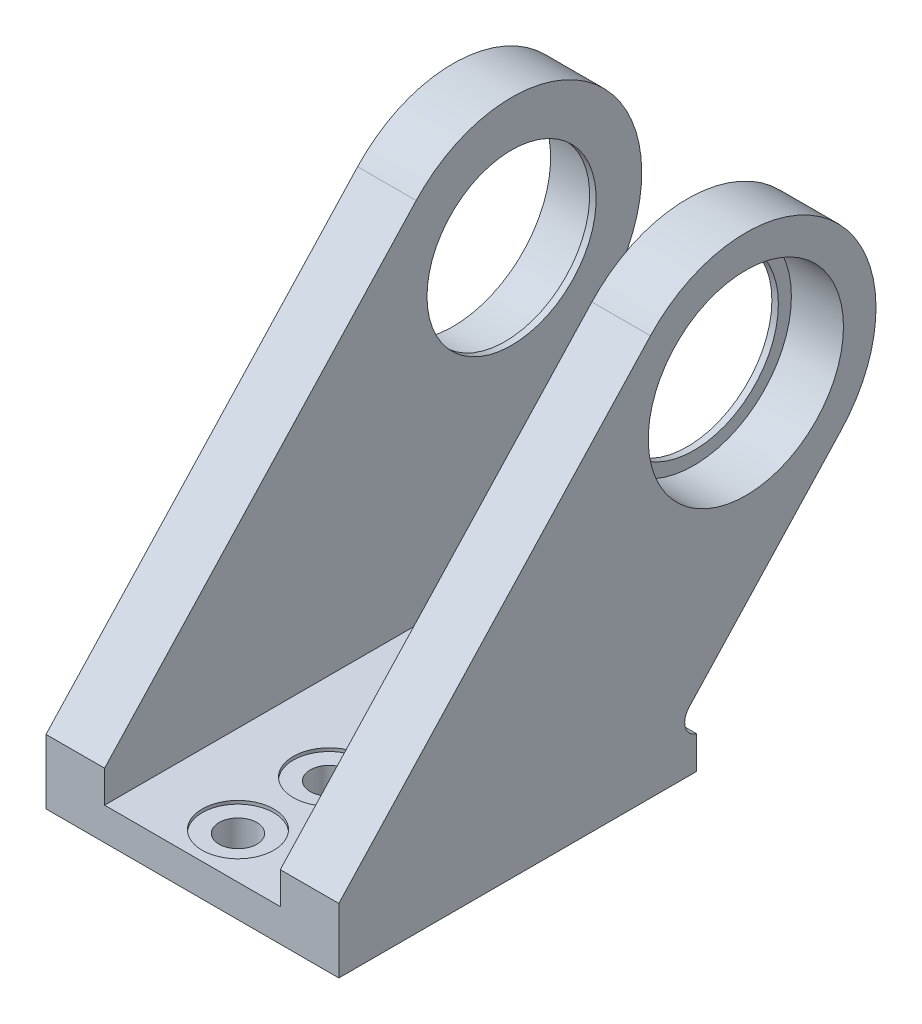
SolidWorks part; units mm, degrees
note: '?' marks a value the reader was unsure of.
ref_plane "前视基准面" through (0, 0, 0) normal (0, 0, 1) x (1, 0, 0)
ref_plane "上视基准面" through (0, 0, 0) normal (0, 1, 0) x (1, 0, 0)
ref_plane "右视基准面" through (0, 0, 0) normal (1, 0, 0) x (0, 0, -1)
sketch "草图1" plane through (0, 0, 0) normal (0, 1, 0) x (1, 0, 0)
  line L1 (0, 0) -> (45, 0)
  line L2 (0, 0) -> (0, 50)
  line L3 (0, 50) -> (45, 50)
  line L4 (45, 0) -> (45, 50)
  dimension "D1" = 50
  dimension "D2" = 45
extrude "凸台-拉伸1" add sketch "草图1" along normal blind 5
sketch "草图2" plane through (45, 0, 0) normal (1, 0, 0) x (0, 0, -1)
  line L0 (0, 5) -> (0, 9.9205)
  line L1 (0, 9.9205) -> (47.8837, 61.5289)
  line L2 (50, 5) -> (0, 5)
  line L3 (77.2063, 34.3226) -> (50, 5)
  arc A0 (77.2063, 34.3226) -> (47.8837, 61.5289) centre (62.545, 47.9258) ccw
  dimension "D1" = 40
  dimension "D2" = 40
extrude "凸台-拉伸2" add sketch "草图2" against normal blind 9
sketch "草图3" plane through (0, 0, 0) normal (-1, 0, 0) x (0, 0, 1)
  line L0 (0, 5) -> (0, 9.9205)
  line L1 (0, 5) -> (-50, 5)
  line L2 (0, 9.9205) -> (-47.8837, 61.5289)
  line L7 (-77.2063, 34.3226) -> (-50, 5)
  arc A2 (-47.8837, 61.5289) -> (-77.2063, 34.3226) centre (-62.545, 47.9258) ccw
extrude "凸台-拉伸3" add sketch "草图3" against normal blind 9
sketch "草图4" plane through (0, 0, 0) normal (-1, 0, 0) x (0, 0, 1)
  circle A1 centre (-62.545, 47.9258) radius 13
extrude "切除-拉伸1" cut sketch "草图4" against normal blind 9
sketch "草图5" plane through (45, 0, 0) normal (1, 0, 0) x (0, 0, -1)
  circle A0 centre (62.545, 47.9258) radius 13
extrude "切除-拉伸2" cut sketch "草图5" against normal blind 9
sketch "草图6" plane through (0, 0, -50) normal (0, 0, -1) x (-1, 0, 0)
  line L1 (-45, 5) -> (0, 5)
  line L2 (-45, 5) -> (-45, 0)
  line L3 (-45, 0) -> (0, 0)
  line L4 (0, 5) -> (0, 0)
extrude "凸台-拉伸4" add sketch "草图6" along normal blind 5
fillet "圆角1" radius 2.5 2 edges at (4.5, 5, -50) (40.5, 5, -50)
ref_axis "基准轴1" through (9, 47.9258, -62.545) along (-1, 0, 0)?
sketch "草图13" plane through (0, 5, 0) normal (0, 1, 0) x (1, 0, 0)
  line L0 (9, 7) -> (36, 7)
  line L1 (9, 0) -> (9, 47.8837) construction
  line L2 (36, 0) -> (36, 55) construction
  line L3 (22.5, 7) -> (22.5, 21)
  line L4 (22.5, 21) -> (22.5, 35)
  line L5 (9, 0) -> (36, 0) construction
  dimension "D1" = 7
  dimension "D2" = 14
  dimension "D3" = 14
hole_wizard "打孔尺寸(%根据六角头螺)栓 C 级的类型1" positions "3D草图1" profile "草图14" counterbore size "M5" standard "GB"
sketch3d "3D草图1"
  point P0 (22.5, 5, -21)
  point P3 (22.5, 5, -7)
  point P6 (22.5, 5, -35)
sketch "草图14" plane through (22.5, 5, -21) normal (1, 0, 0) x (0, 0, 1)
  line L0 (0, 0) -> (0, 6.7425)
  line L1 (0, 6.7425) -> (2.9, 5)
  line L2 (2.9, 5) -> (2.9, 0.5)
  line L3 (2.9, 0.5) -> (5.5, 0.5)
  line L4 (5.5, 0.5) -> (5.5, 0)
  line L5 (5.5, 0) -> (0, 0)
  line L10 (0, 6.7425) -> (-2.9, 5) construction
  line L11 (0, -6.35) -> (0, 107.95) construction
  dimension "孔直径" = 5.8
  dimension "孔深度" = 5
  dimension "柱形沉头孔直径" = 11
  dimension "柱形沉头孔深度" = 0.5
  dimension "导头角度" = 118
sketch "草图15" plane through (0, 0, 0) normal (-1, 0, 0) x (0, 0, 1)
  circle A0 centre (-62.545, 47.9258) radius 15
extrude "切除-拉伸3" cut sketch "草图15" against normal blind 8
sketch "草图16" plane through (45, 0, 0) normal (1, 0, 0) x (0, 0, -1)
  circle A0 centre (62.545, 47.9258) radius 15
extrude "切除-拉伸4" cut sketch "草图16" against normal blind 8
